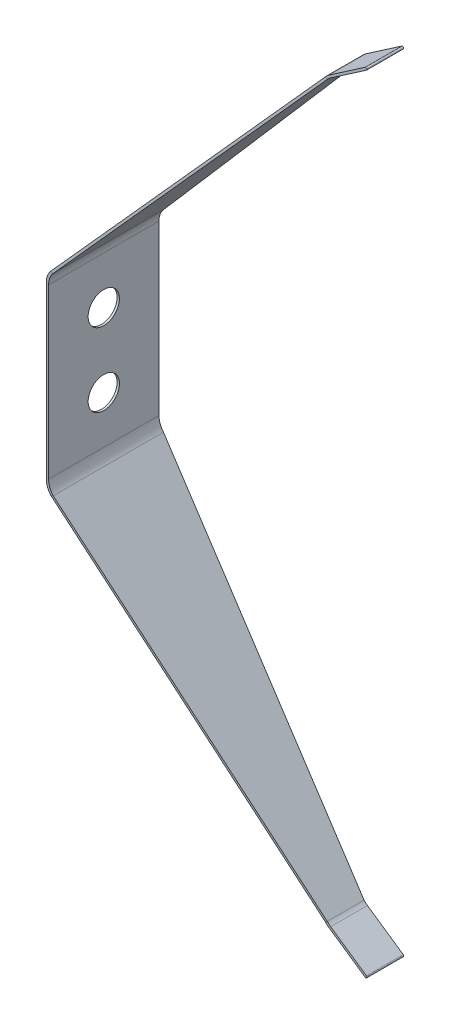
SolidWorks part; units mm, degrees
material "Acciaio al carbonio semplice"
ref_plane "Piano frontale" through (0, 0, 0) normal (0, 0, 1) x (1, 0, 0)
ref_plane "Piano superiore" through (0, 0, 0) normal (0, 1, 0) x (1, 0, 0)
ref_plane "Piano destro" through (0, 0, 0) normal (1, 0, 0) x (0, 0, -1)
sketch "Schizzo1" plane through (0, 0, 0) normal (0, 0, 1) x (1, 0, 0)
  line L3 (0, -10) -> (0, 10)
  line L13 (0, 10) -> (26.5418, 40)
  line L14 (26.5418, 40) -> (30.6624, 42.832)
  line L15 (0, 0) -> (8.9599, 0) construction
  line L16 (26.5418, -40) -> (30.6624, -42.832)
  line L17 (0, -10) -> (26.5418, -40)
  line L18 (26.7087, -39.8114) -> (30.804, -42.626)
  line L19 (0.25, -9.9053) -> (26.7087, -39.8114)
  line L20 (0.25, -9.9053) -> (0.25, 9.9053)
  line L21 (0.25, 9.9053) -> (26.7087, 39.8114)
  line L22 (26.7087, 39.8114) -> (30.804, 42.626)
  arc A8 (30.6624, -42.832) -> (30.804, -42.626) centre (30.7332, -42.729) ccw
  arc A9 (30.6624, 42.832) -> (30.804, 42.626) centre (30.7332, 42.729) cw
  dimension "D6" = 0.25
  dimension "D1" = 10
  dimension "D2" = 40
  dimension "D3" = 41.5
  dimension "D4" = 5
  dimension "D5" = 55.5
  dimension "D7" = 40.0558
extrude "Estrusione-Estrusione1" add sketch "Schizzo1" along normal blind 6 and the other way blind 6
hole_wizard "Foro per Vite M3-1" positions "Schizzo2" profile "Schizzo3" hole size "M3" standard "ISO" end condition through all
sketch "Schizzo2" plane through (0.25, 0, 0) normal (1, 0, 0) x (0, 0, -1)
  point P0 (0, 4)
  point P2 (0, -4)
  dimension "D1" = 4
  dimension "D2" = 4
sketch "Schizzo3" plane through (0.25, 4, 0) normal (0, 1, 0) x (0, 0, -1)
  line L0 (0, 0) -> (0, 0.25)
  line L1 (0, 0.25) -> (1.7, 0.25)
  line L2 (1.7, 0.25) -> (1.7, 0)
  line L5 (1.7, 0) -> (0, 0)
  line L11 (0, -6.35) -> (0, 107.95) construction
  dimension "Thru Hole Dia." = 3.4
  dimension "Thru Hole Depth" = 0.25
fillet "Raccordo1" radius 2 1 edges at (0, 10, 0) type face fillet first side face at (0, 4, -1.7) second side face at (13.2709, 25, 0)
fillet "Raccordo2" radius 2 1 edges at (0, -10, 0) type face fillet first side face at (0, 4, -1.7) second side face at (13.2709, -25, 0)
fillet "Raccordo3" radius 2 1 edges at (26.5418, -40, 0) type face fillet first side face at (7.012, -17.9256, 1.5) second side face at (28.6021, -41.416, 0)
fillet "Raccordo4" radius 2 1 edges at (26.5418, 40, 0) type face fillet first side face at (20.0318, 32.6419, -1.5) second side face at (28.6021, 41.416, 0)
fillet "Raccordo5" radius 2 1 edges at (0.25, -9.9053, 0) type face fillet first side face at (0.25, 4, -1.7) second side face at (13.4793, -24.8583, 0)
fillet "Raccordo6" radius 2 1 edges at (0.25, 9.9053, 0) type face fillet first side face at (0.25, 4, -1.7) second side face at (13.4793, 24.8583, 0)
fillet "Raccordo7" radius 2 1 edges at (26.7087, 39.8114, 0) type face fillet first side face at (13.7304, 25.1421, 0) second side face at (28.7563, 41.2187, 0)
fillet "Raccordo8" radius 2 1 edges at (26.7087, -39.8114, 0) type face fillet first side face at (13.7304, -25.1421, 0) second side face at (28.7563, -41.2187, 0)
sketch "Schizzo4" plane through (-4.9627, 4.3907, 0) normal (-0.749, 0.6626, 0) x (0, 0, 1)
  line L0 (-2, 47.2998) -> (2, 47.2998) construction
  line L1 (6, 47.2998) -> (-6, 47.2998) construction
  line L2 (2, 47.2998) -> (6, 8.2473)
  line L3 (-2, 47.2998) -> (-6, 8.2473)
  line L4 (-2, 47.2998) -> (-2, 59.8467)
  line L5 (-2, 59.8467) -> (2, 59.8467) construction
  line L6 (2, 59.8467) -> (2, 47.2998)
  line L7 (-6, 8.2473) -> (6, 8.2473) construction
  line L8 (-6, 8.2473) -> (6, 8.2473) construction
  line L9 (-6, 8.2473) -> (-6, 59.8467)
  line L10 (-6, 59.8467) -> (-2, 59.8467)
  line L11 (2, 59.8467) -> (6, 59.8467)
  line L12 (6, 59.8467) -> (6, 8.2473)
  point P7 (0, 47.2998)
  point P11 (0, 8.2473)
  dimension "D1" = 4
extrude "Taglio-Estrusione2" cut sketch "Schizzo4" against normal through all
sketch "Schizzo6" plane through (-4.9627, -4.3907, 0) normal (-0.749, -0.6626, 0) x (0, 0, 1)
  line L0 (6, -8.2473) -> (-6, -8.2473) construction
  line L1 (6, -8.2473) -> (-6, -8.2473)
  line L2 (-6, -8.2473) -> (-2, -47.2998)
  line L3 (-6, -47.2998) -> (6, -47.2998) construction
  line L4 (-2, -47.2998) -> (2, -47.2998) construction
  line L5 (2, -47.2998) -> (6, -8.2473)
  line L6 (-2, -47.2998) -> (-2, -59.492)
  line L7 (-2, -59.492) -> (-6, -59.492)
  line L8 (-6, -59.492) -> (-6, -8.2473)
  line L9 (6, -8.2473) -> (6, -59.492)
  line L10 (6, -59.492) -> (2, -59.492)
  line L11 (2, -59.492) -> (2, -47.2998)
  point P2 (0, -47.2998)
  point P11 (0, -8.2473)
  line M5 (-6, -8.2473) -> (-6, -47.2998)
  line M6 (-6, -47.2998) -> (6, -47.2998)
  line M7 (6, -47.2998) -> (6, -8.2473)
  dimension "D1" = 4
extrude "Taglio-Estrusione3" cut sketch "Schizzo6" against normal through all contours L2 M5 M6 | L8 L7 L6 M6 | L11 L10 L9 M6 | L5 M6 M7 region at (17.7534, -30.0666, 4.6667) region at (17.7534, -30.0666, -4.6667) region at (30.4184, -44.3818, 4) region at (30.4184, -44.3818, -4)
